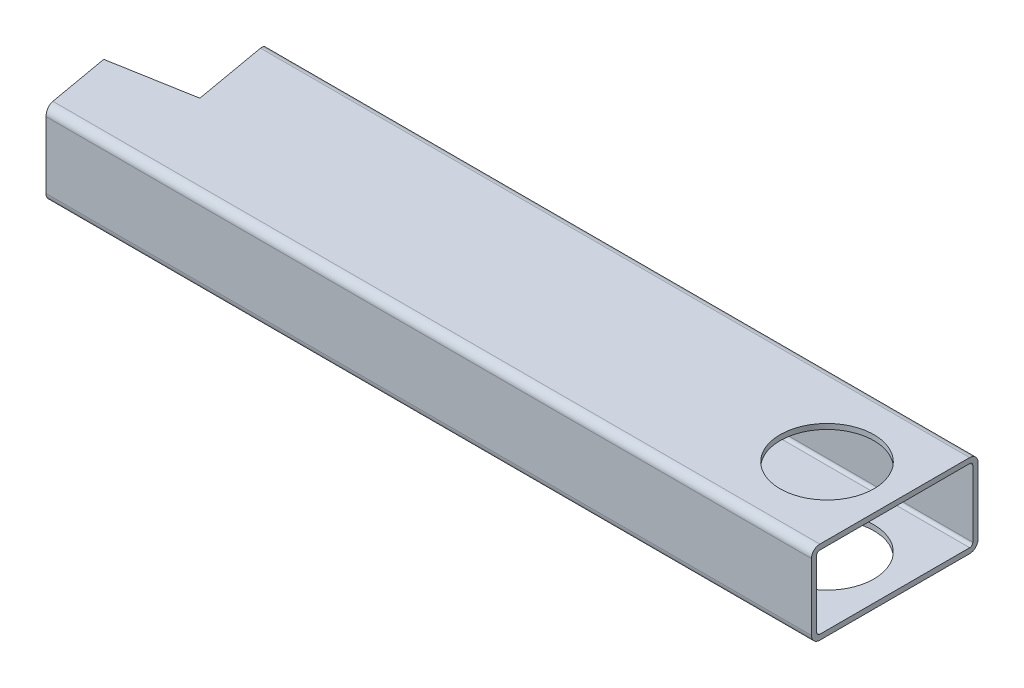
SolidWorks part; units mm, degrees
material "6061 Alloy"
ref_plane "Front" through (0, 0, 0) normal (0, 0, 1) x (1, 0, 0)
ref_plane "Top" through (0, 0, 0) normal (0, 1, 0) x (1, 0, 0)
ref_plane "Right" through (0, 0, 0) normal (1, 0, 0) x (0, 0, -1)
sketch "Sketch1" plane through (0, 0, 0) normal (1, 0, 0) x (0, 0, -1)
  line L1 (-2.54, 0) -> (-48.26, 0)
  line L2 (0, 2.54) -> (0, 22.86)
  line L3 (-2.54, 25.4) -> (-48.26, 25.4)
  line L4 (-50.8, 2.54) -> (-50.8, 22.86)
  arc A0 (-50.8, 2.54) -> (-48.26, 0) centre (-48.26, 2.54) ccw
  arc A1 (-2.54, 0) -> (0, 2.54) centre (-2.54, 2.54) ccw
  arc A2 (0, 22.86) -> (-2.54, 25.4) centre (-2.54, 22.86) ccw
  arc A3 (-48.26, 25.4) -> (-50.8, 22.86) centre (-48.26, 22.86) ccw
  point P7 (-50.8, 0)
  point P10 (0, 0)
  point P13 (0, 25.4)
  dimension "D3" = 2.54
  dimension "D1" = 25.4
  dimension "D2" = 50.8
extrude "Extrude-Thin1" add sketch "Sketch1" against normal blind 243.6368 thin thin type one direction reverse wall 1.5875
sketch "Sketch3" plane through (0, 25.4, 0) normal (0, 1, 0) x (1, 0, 0)
  line L0 (0, 49.2125) -> (79.6022, 243.0747)
  line L1 (0, -1.5875) -> (25.4, -1.5875)
  line L2 (0, -1.5875) -> (0, 49.2125)
  line L3 (0, 49.2125) -> (25.4, 49.2125)
  line L4 (25.4, -1.5875) -> (25.4, 49.2125)
  line L5 (79.6022, 243.0747) -> (126.5949, 223.7789)
  line L6 (126.5949, 223.7789) -> (34.0567, -1.5875)
  line L7 (71.7537, 223.9604) -> (118.7463, 204.6646) construction
  line L8 (95.25, 214.3125) -> (0, 214.3125)
  line L9 (0, 49.2125) -> (0, 289.0515)
  line L10 (25.4, -1.5875) -> (34.0567, -1.5875)
  circle A0 centre (95.25, 214.3125) radius 14.3129
  point P11 (95.25, 214.3125)
  dimension "D4" = 28.6258
  dimension "D5" = 6.35
  dimension "D1" = 25.4
  dimension "D2" = 50.8
  dimension "D3" = 50.8
  dimension "D6" = 95.25
  dimension "D7" = 165.1
  dimension "D8" = 243.6254
  dimension "D9" = 209.5687
sketch "Sketch4" plane through (0, 25.4, 0) normal (0, 1, 0) x (1, 0, 0)
  line L0 (-20.6629, -48.26) -> (-20.6629, -2.54) construction
  line L2 (-243.6368, -2.54) -> (0, -2.54) construction
  line L3 (-243.6368, -48.26) -> (0, -48.26) construction
  line L4 (0, -2.54) -> (0, -48.26) construction
  line L5 (0, 0) -> (-216.7798, 0) construction
  line L6 (-243.6368, 0) -> (0, 0) construction
  line L7 (-216.7798, 0) -> (-212.3692, -25.0141)
  line L8 (-212.3692, -25.0141) -> (-237.2868, -29.4078)
  line L9 (-237.2868, -29.4078) -> (-233.5148, -50.8)
  line L10 (-243.6368, -50.8) -> (0, -50.8) construction
  line L11 (-216.7798, 0) -> (-243.6368, 0)
  line L12 (-243.6368, 0) -> (-243.6368, -30.5274)
  line L13 (-233.5148, -50.8) -> (-243.6368, -50.8)
  line L14 (-243.6368, -50.8) -> (-243.6368, -30.5274)
  line L15 (-243.6368, -30.5274) -> (-212.3692, -25.0141) construction
  circle A0 centre (-20.6629, -25.4) radius 14.3129
  point P5 (-20.6629, -25.4)
  dimension "D1" = 28.6258
  dimension "D2" = 6.35
  dimension "D3" = 25.4
  dimension "D4" = 31.75
  dimension "D5" = 80
  dimension "D6" = 6.35
extrude "Cut-Extrude1" cut sketch "Sketch4" against normal through all and the other way through all
